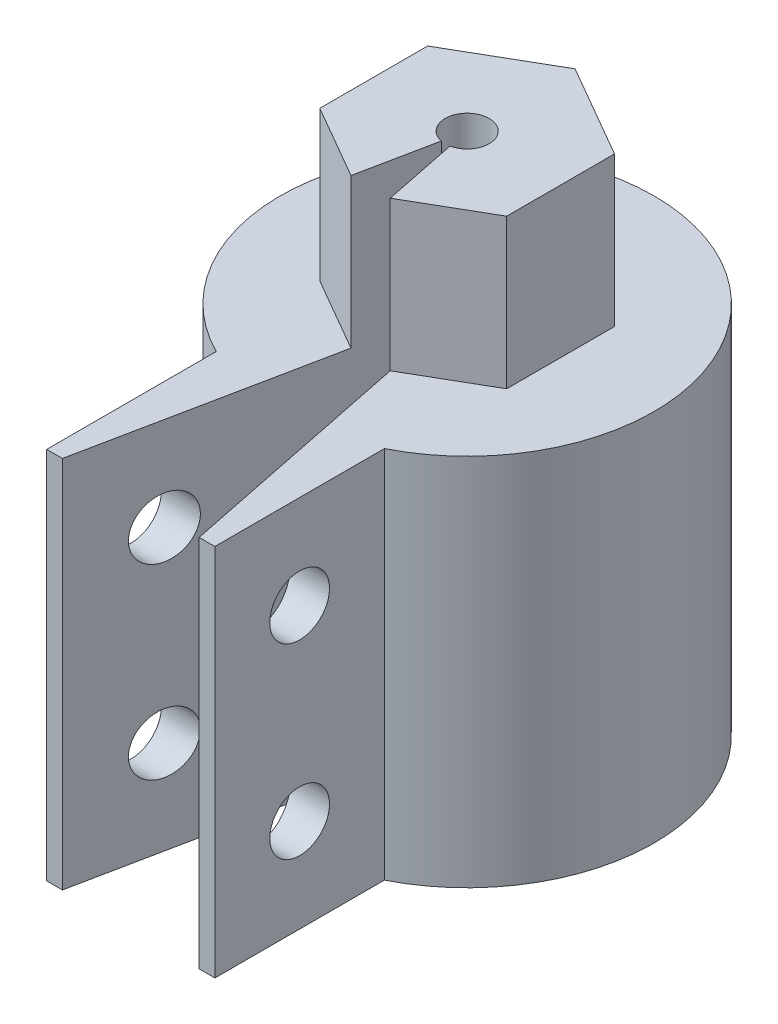
SolidWorks part; units mm, degrees
ref_plane "正面" through (0, 0, 0) normal (0, 0, 1) x (1, 0, 0)
ref_plane "平面" through (0, 0, 0) normal (0, 1, 0) x (1, 0, 0)
ref_plane "右側面" through (0, 0, 0) normal (1, 0, 0) x (0, 0, -1)
sketch "ｽｹｯﾁ1" plane through (0, 0, 0) normal (0, 1, 0) x (1, 0, 0)
  line L6 (-4.5, -8.9303) -> (-4.5, -18)
  line L7 (-4.5, -18) -> (4.5, -18)
  line L8 (4.5, -8.9303) -> (4.5, -18)
  arc A0 (4.5, -8.9303) -> (-4.5, -8.9303) centre (0, 0) ccw
  point P1 (0, -18)
  dimension "D1" = 20
  dimension "D3" = 9
  dimension "D4" = 18
extrude "ﾎﾞｽ - 押し出し1" add sketch "ｽｹｯﾁ1" along normal blind 20
sketch "ｽｹｯﾁ2" plane through (0, 20, 0) normal (0, 1, 0) x (1, 0, 0)
  line L5 (0, 5.7735) -> (-5, 2.8868)
  line L6 (-5, 2.8868) -> (-5, -2.8868)
  line L7 (-5, -2.8868) -> (0, -5.7735)
  line L8 (0, -5.7735) -> (5, -2.8868)
  line L9 (5, -2.8868) -> (5, 2.8868)
  line L10 (5, 2.8868) -> (0, 5.7735)
  circle A0 centre (0, 0) radius 5 construction
  dimension "D1" = 10
extrude "ﾎﾞｽ - 押し出し2" add sketch "ｽｹｯﾁ2" along normal blind 8
sketch "ｽｹｯﾁ3" plane through (0, 28, 0) normal (0, 1, 0) x (1, 0, 0)
  line L5 (-4.5, -18) -> (4.5, -18) construction
  line L6 (-3.6587, -18) -> (-0.234, -1.1515)
  line L7 (0.234, -1.1515) -> (3.6587, -18)
  arc A1 (0.234, -1.1515) -> (-0.234, -1.1515) centre (0, 0) ccw
  arc A2 (-3.6587, -18) -> (3.6587, -18) centre (0, 0) ccw
  point P1 (0, -18.3681)
  dimension "D1" = 2.35
  dimension "D2" = 6.9115
extrude "ｶｯﾄ - 押し出し1" cut sketch "ｽｹｯﾁ3" against normal through all
sketch "ｽｹｯﾁ4" plane through (-4.5, 0, 0) normal (-1, 0, 0) x (0, 0, 1)
  line L0 (8.9303, 20) -> (18, 20) construction
  line L1 (8.9303, 0) -> (18, 0) construction
  circle A0 centre (13.4651, 15) radius 1.6
  circle A1 centre (13.4651, 5) radius 1.6
  point P8 (13.4651, 20)
  dimension "D3" = 3.2
  dimension "D1" = 5
  dimension "D2" = 5
extrude "ｶｯﾄ - 押し出し2" cut sketch "ｽｹｯﾁ4" against normal through all
equation "\"D2@ｽｹｯﾁ3\"=PI*(2.2)"
